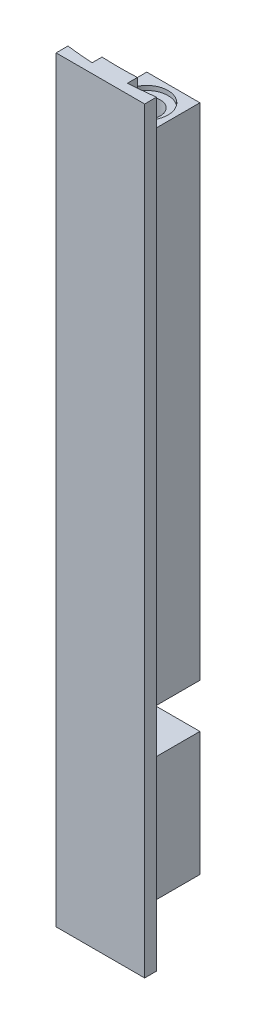
SolidWorks part; units mm, degrees
ref_plane "Front Plane" through (0, 0, 0) normal (0, 0, 1) x (1, 0, 0)
ref_plane "Top Plane" through (0, 0, 0) normal (0, 1, 0) x (1, 0, 0)
ref_plane "Right Plane" through (0, 0, 0) normal (1, 0, 0) x (0, 0, -1)
ref_plane "Plane7" through (0, -5, 0) normal (0, -1, 0) x (-1, 0, 0)
sketch "Sketch1" plane through (0, 0, 0) normal (0, 1, 0) x (1, 0, 0)
  circle A0 centre (0, 0) radius 37.5 construction
  dimension "D1" = 75
sketch "Sketch3" plane through (0, -5, 0) normal (0, -1, 0) x (1, 0, 0)
  line L0 (-3, 37.3798) -> (-3, 31.3798)
  line L1 (-3, 31.3798) -> (3, 31.3798)
  line L2 (3, 31.3798) -> (3, 37.3798)
  line L9 (0, 40.3758) -> (0, -39.6162) construction
  line L10 (0, -41.25) -> (0, 41.25) construction
  arc A0 (3, 37.3798) -> (-3, 37.3798) centre (0, 0) ccw
  circle A4 centre (0, 0) radius 37.5 construction
  dimension "D2" = 6
  dimension "D3" = 6
extrude "Boss-Extrude2" add sketch "Sketch3" along normal blind 75.5
sketch "Sketch5" plane through (0, 0, 0) normal (0, 1, 0) x (1, 0, 0)
  line L0 (-5, -38.2785) -> (-5, -39.2364)
  line L1 (5, -38.2785) -> (5, -39.2833)
  line L2 (2, -38.5518) -> (2, -37.4318)
  line L3 (-2, -38.5518) -> (-2, -37.4318)
  line L12 (0, 40.7328) -> (0, -41.0085) construction
  line L13 (0, -44.275) -> (0, 44.275) construction
  line L14 (0, -39.6211) -> (-5, -39.6211)
  line L15 (-5, -39.6211) -> (-5, -39.2364)
  line L16 (0, -39.6211) -> (5, -39.6211)
  line L17 (5, -39.6211) -> (5, -39.2833)
  arc A1 (-2, -37.4318) -> (2, -37.4318) centre (0, 0) ccw
  arc A2 (5, -38.2785) -> (2, -38.5518) centre (0, 0) cw
  arc A3 (-5, -38.2785) -> (-2, -38.5518) centre (0, 0) ccw
  circle A13 centre (0, 0) radius 37.5 construction
  dimension "D1" = 4
  dimension "D2" = 10
  dimension "D3" = 1.12
  dimension "D4" = 1.0049
  dimension "D5" = 1.0693
extrude "Boss-Extrude3" add sketch "Sketch5" against normal blind 85.5
sketch "Sketch7" plane through (0, 0, 0) normal (1, 0, 0) x (0, 0, -1)
  line L0 (0, 41.25) -> (0, -41.25) construction
  line L1 (0, -61.5) -> (-37.5, -61.5)
  line L2 (0, -61.5) -> (0, -66.5)
  line L3 (0, -66.5) -> (-37.5, -66.5)
  line L4 (-37.5, -61.5) -> (-37.5, -66.5)
  line L6 (-31.3798, -80.5) -> (-37.3798, -80.5) construction
  line L7 (0, -27.0167) -> (0, -72.0117) construction
  dimension "D1" = 37.5
  dimension "D2" = 5
  dimension "D3" = 14
revolve "Cut-Revolve1" cut sketch "Sketch7" angle 360 about L7
ref_plane "Plane5" through (0, -80.5, 0) normal (0, -1, 0) x (-1, 0, 0)
sketch "Sketch9" plane through (0, -80.5, 0) normal (0, -1, 0) x (-1, 0, 0)
  line L0 (0, -31.1751) -> (0, -37.6667) construction
  line L1 (0, 44.275) -> (0, -44.275) construction
  line L2 (-3.1738, -34.4209) -> (3.1592, -34.4209) construction
  circle A0 centre (0, -34.4209) radius 1.55
  dimension "D2" = 3.1
extrude "Cut-Extrude4" cut sketch "Sketch9" against normal blind 4.3
sketch "Sketch10" plane through (0, -80.5, 0) normal (0, -1, 0) x (-1, 0, 0)
  line L0 (0, -31.1751) -> (0, -37.6667) construction
  line L2 (-3.1738, -34.4209) -> (3.1592, -34.4209) construction
  circle A0 centre (0, -34.4209) radius 2.4
  dimension "D2" = 4.8
extrude "Cut-Extrude5" cut sketch "Sketch10" against normal blind 0.5
sketch "Sketch12" plane through (0, -5, 0) normal (0, -1, 0) x (-1, 0, 0)
  circle A0 centre (0, 0) radius 37.5 construction
sketch "Sketch13" plane through (0, -5, 0) normal (0, -1, 0) x (-1, 0, 0)
  line L0 (0, -31.134) -> (0, -37.6256) construction
  line L1 (-2.6479, -34.3798) -> (2.8747, -34.3798) construction
  line L2 (3, -37.3798) -> (3, -31.3798) construction
  line L3 (-3, -31.3798) -> (-3, -37.3798) construction
  circle A0 centre (0, -34.3798) radius 2.4
sketch "Sketch14" plane through (0, -5, 0) normal (0, -1, 0) x (-1, 0, 0)
  line L0 (0, -31.134) -> (0, -37.6256) construction
  line L2 (-3.1738, -34.3798) -> (3.1592, -34.3798) construction
  line L3 (3, -37.3798) -> (3, -31.3798) construction
  line L4 (-3, -31.3798) -> (-3, -37.3798) construction
  circle A0 centre (0, -34.3798) radius 1.55
  dimension "D2" = 3.1
extrude "Cut-Extrude6" cut sketch "Sketch13" along normal blind 0.5
extrude "Cut-Extrude7" cut sketch "Sketch14" along normal blind 4.3
